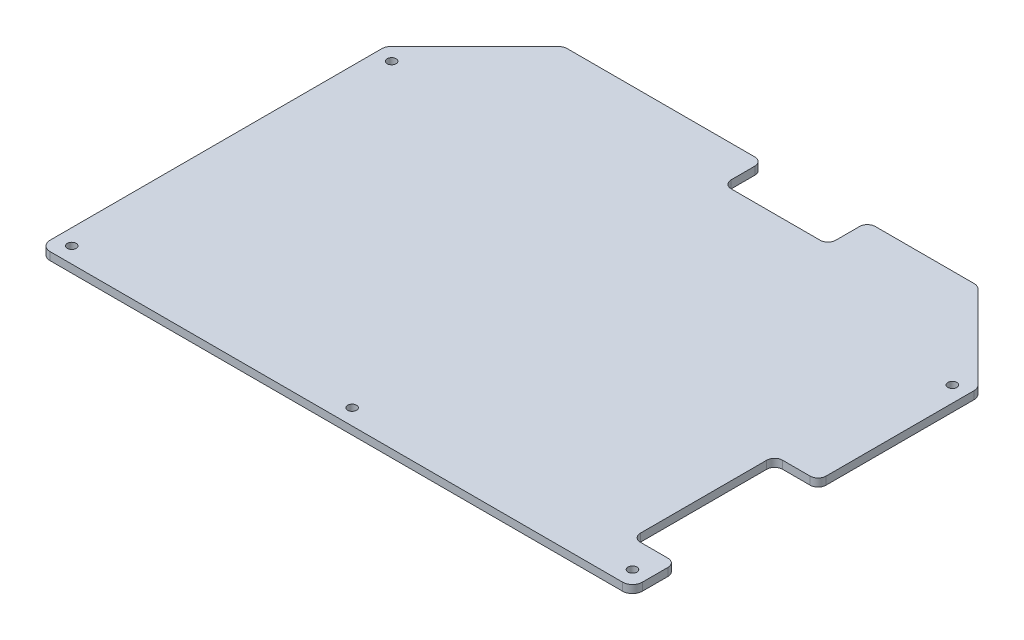
SolidWorks part; units mm, degrees
material "Acier non allié"
ref_plane "Front" through (0, 0, 0) normal (0, 0, 1) x (1, 0, 0)
ref_plane "Top" through (0, 0, 0) normal (0, 1, 0) x (1, 0, 0)
ref_plane "Right" through (0, 0, 0) normal (1, 0, 0) x (0, 0, -1)
sketch "Main scetch" plane through (0, 0, 0) normal (0, 1, 0) x (1, 0, 0)
  line L0 (-150, 0) -> (150, 0)
  line L1 (0, 0) -> (150, 0) construction
  line L2 (0, 0) -> (0, 220) construction
  line L3 (0, 220) -> (150, 220) construction
  line L4 (150, 0) -> (150, 220) construction
  line L5 (150, 0) -> (150, 175)
  line L6 (150, 175) -> (105, 220)
  line L10 (105, 220) -> (-105, 220)
  line L11 (-150, 0) -> (-150, 175)
  line L12 (-150, 175) -> (-105, 220)
  dimension "D1" = 150
  dimension "D2" = 220
  dimension "D3" = 45
  dimension "D4" = 45
extrude "Main extrusion" add sketch "Main scetch" along normal blind 4
fillet "Corner leave" radius 5 6 edges at (-150, 2, 0) (150, 2, -175) (105, 2, -220) (150, 2, 0) (-105, 2, -220) (-150, 2, -175)
sketch "Esquisse1" plane through (0, 4, 0) normal (0, 1, 0) x (1, 0, 0)
  line L0 (-145, 0) -> (145, 0) construction
  line L1 (-150, 172.9289) -> (-150, 5) construction
  line L3 (0, 0) -> (0, 62.3031) construction
  line L4 (150, 5) -> (150, 172.9289) construction
  circle A0 centre (-142, 8) radius 1
  circle A1 centre (-142, 170) radius 1
  circle A4 centre (142, 170) radius 1
  circle A5 centre (142, 8) radius 1
  circle A6 centre (0, 8) radius 1.5
  dimension "D3" = 2
  dimension "D6" = 2
  dimension "D8" = 8
  dimension "D15" = 2
  dimension "D18" = 2
  dimension "D7" = 3
  dimension "D1" = 8
  dimension "D2" = 8
  dimension "D4" = 8
  dimension "D5" = 170
  dimension "D13" = 170
  dimension "D14" = 8
  dimension "D16" = 8
  dimension "D17" = 8
hole_wizard "Dégagement M41" positions "Esquisse2" profile "Esquisse3" hole size "M4" standard "ISO" end condition through all
sketch "Esquisse2" plane through (0, 4, 0) normal (0, 1, 0) x (1, 0, 0)
  point P0 (-142, 8)
  point P3 (-142, 170)
  point P6 (142, 170)
  point P9 (142, 8)
  point P12 (0, 8)
sketch "Esquisse3" plane through (-142, 4, -8) normal (1, 0, 0) x (0, 0, 1)
  line L0 (0, 0) -> (0, 4)
  line L1 (0, 4) -> (2.25, 4)
  line L2 (2.25, 4) -> (2.25, 0)
  line L5 (2.25, 0) -> (0, 0)
  line L11 (0, -6.35) -> (0, 107.95) construction
  dimension "Diamètre du perçage jusqu'au prochain" = 4.5
  dimension "Profondeur du perçage jusqu'au prochain" = 4
sketch "Esquisse4" plane through (0, 4, 0) normal (0, 1, 0) x (1, 0, 0)
  line L0 (150, 5) -> (150, 172.9289) construction
  line L3 (128, 22) -> (150, 22)
  line L5 (-145, 0) -> (145, 0) construction
  line L7 (128, 94) -> (150, 94)
  line L8 (128, 94) -> (128, 22)
  line L10 (150, 94) -> (150, 22)
  point P0 (150, 24.4206)
  dimension "D1" = 22
  dimension "D2" = 72
  dimension "D6" = 22
extrude "Enlèv. mat.-Extru.1" cut sketch "Esquisse4" against normal up to surface (4 mm away) up to face at (-142, 0, -5.75)
sketch "Esquisse5" plane through (0, 4, 0) normal (0, 1, 0) x (1, 0, 0)
  line L0 (150, 94) -> (150, 172.9289) construction
  line L3 (36.3, 200) -> (49, 200)
  line L4 (49, 220) -> (49, 200)
  line L5 (102.9289, 220) -> (-102.9289, 220) construction
  line L7 (-4, 220) -> (49, 220)
  line L8 (-4, 220) -> (-4, 200)
  line L9 (-4, 200) -> (36.3, 200)
  point P6 (34.8358, 200)
  point P10 (0, 0)
  point P12 (47.5807, 220)
  point P13 (34.9449, 220)
  point P14 (47.1257, 220)
  dimension "D1" = 101
  dimension "D2" = 53
  dimension "D5" = 20
extrude "Enlèv. mat.-Extru.2" cut sketch "Esquisse5" against normal up to surface (4 mm away) up to face at (-142, 0, -5.75)
fillet "Congé1" radius 4 8 edges at (49, 2, -220) (-4, 2, -220) (150, 2, -22) (150, 2, -94) (128, 2, -22) (128, 2, -94) (49, 2, -200) (-4, 2, -200)
equation "\"WIDTH\"= 300mm'Total width of the robot"
equation "\"LENGTH\"= 220mm'Total length of the robot"
equation "\"D1@Main scetch\" = \"WIDTH\" / 2"
equation "\"D2@Main scetch\" = \"LENGTH\""
equation "\"CUT_DEPTH\"= 45mm'Depth of the cut on the edges of the plate"
equation "\"D3@Main scetch\" = \"CUT_DEPTH\""
equation "\"D4@Main scetch\" = \"CUT_DEPTH\""
equation "\"Plate_th\"= 3mm'Thickness of the plate"
equation "\"D1\"= \"Plate_th\""
